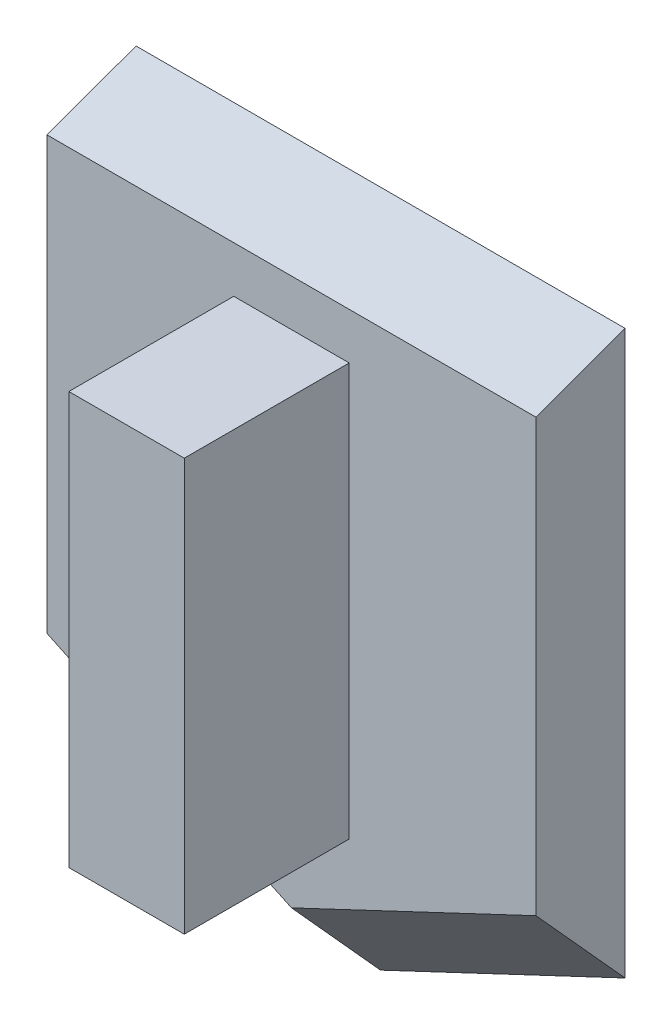
SolidWorks part; units mm, degrees
ref_plane "Plano frontal" through (0, 0, 0) normal (0, 0, 1) x (1, 0, 0)
ref_plane "Plano superior" through (0, 0, 0) normal (0, 1, 0) x (1, 0, 0)
ref_plane "Plano direito" through (0, 0, 0) normal (1, 0, 0) x (0, 0, -1)
sketch "Esboço1" plane through (0, 0, 0) normal (0, 0, 1) x (1, 0, 0)
  line L0 (-14.825, -17.5) -> (0, -24.5)
  line L1 (-14.825, 17.5) -> (14.825, 17.5)
  line L2 (-14.825, 17.5) -> (-14.825, -17.5)
  line L4 (14.825, 17.5) -> (14.825, -17.5)
  line L5 (-14.825, 17.5) -> (14.825, -17.5) construction
  line L6 (-14.825, -17.5) -> (14.825, 17.5) construction
  line L7 (0, -24.5) -> (14.825, -17.5)
  point P0 (0, 0)
  point P6 (0, 0)
  point P8 (0, 0)
  dimension "D1" = 7
  dimension "D2" = 29.65
  dimension "D3" = 35
extrude "Ressalto-extrusão1" add sketch "Esboço1" along normal blind 5.4
chamfer "Chanfro1" distance 6 angle 45 2 edges at (7.4125, -21, 5.4) (-7.4125, -21, 5.4)
sketch "Esboço2" plane through (0, 0, 5.4) normal (0, 0, 1) x (1, 0, 0)
  line L1 (-3.5, 12.5) -> (3.5, 12.5)
  line L2 (-3.5, 12.5) -> (-3.5, -12.5)
  line L3 (-3.5, -12.5) -> (3.5, -12.5)
  line L4 (3.5, 12.5) -> (3.5, -12.5)
  line L5 (-3.5, 12.5) -> (3.5, -12.5) construction
  line L6 (-3.5, -12.5) -> (3.5, 12.5) construction
  point P0 (0, 0)
  dimension "D1" = 7
  dimension "D2" = 25
extrude "Ressalto-extrusão2" add sketch "Esboço2" along normal blind 10
chamfer "Chanfro2" distance 6 angle 20 1 edges at (0, 17.5, 5.4) first distance on face at (0, 17.5, 2.7)
